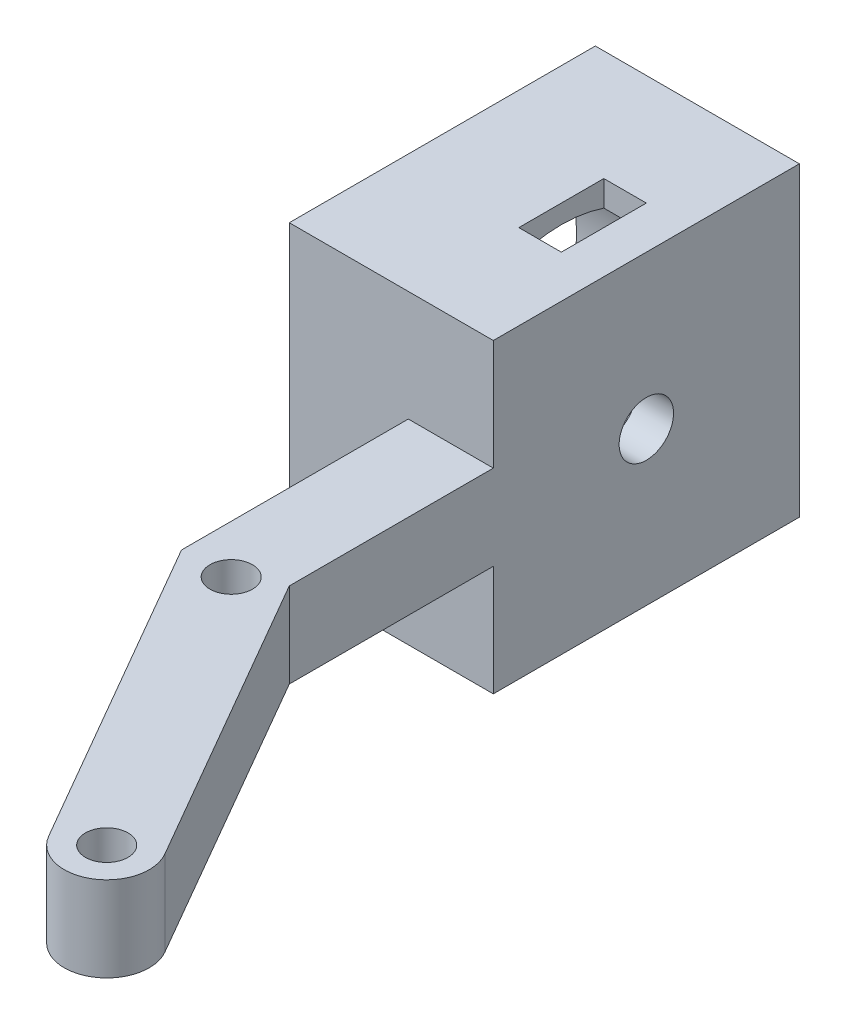
SolidWorks part; units mm, degrees
material "AISI 316 Stainless Steel Sheet (SS)"
ref_plane "Front Plane" through (0, 0, 0) normal (0, 0, 1) x (1, 0, 0)
ref_plane "Top Plane" through (0, 0, 0) normal (0, 1, 0) x (1, 0, 0)
ref_plane "Right Plane" through (0, 0, 0) normal (1, 0, 0) x (0, 0, -1)
sketch "Sketch1" plane through (0, 0, 0) normal (0, 1, 0) x (1, 0, 0)
  line L0 (-6.35, -14.4015) -> (-6.35, 2.54)
  line L1 (0, -12.7) -> (0, 25.4)
  line L2 (0, 25.4) -> (-15.24, 25.4)
  line L3 (-15.24, 25.4) -> (-15.24, 2.54)
  line L4 (-15.24, 2.54) -> (-6.35, 2.54)
  line L5 (0, -12.7) -> (12.7, -34.697)
  line L6 (-6.35, -14.4015) -> (7.2007, -37.872)
  line L7 (0, -12.7) -> (-5.4993, -15.875) construction
  arc A0 (7.2007, -37.872) -> (12.7, -34.697) centre (9.9504, -36.2845) ccw
  circle A1 centre (9.9504, -36.2845) radius 1.5875
  circle A2 centre (-2.7496, -14.2875) radius 1.5875
  dimension "D1" = 3.175
  dimension "D2" = 3.175
  dimension "D6" = 3.175
  dimension "D3" = 150
  dimension "D4" = 6.35
  dimension "D8" = 25.4
  dimension "D10" = 15.24
  dimension "D11" = 38.1
  dimension "D12" = 22.86
  dimension "D13" = 12.7
extrude "Boss-Extrude1" add sketch "Sketch1" along normal blind 22.86
sketch "Sketch2" plane through (0, 22.86, 0) normal (0, 1, 0) x (1, 0, 0)
  line L1 (-6.35, -14.4015) -> (8.7882, -40.6217)
  line L2 (0, -12.7) -> (14.2875, -37.4467)
  line L3 (14.2875, -37.4467) -> (8.7882, -40.6217)
  line L4 (-6.35, -14.4015) -> (7.2007, -37.872) construction
  line L5 (12.7, -34.697) -> (0, -12.7) construction
  line L6 (-6.35, 2.54) -> (0, 2.54)
  line L7 (0, -12.7) -> (0, 25.4) construction
  line L8 (0, 2.54) -> (0, -12.7)
  line L9 (-6.35, -14.4015) -> (-6.35, 2.54)
  arc A0 (7.2007, -37.872) -> (12.7, -34.697) centre (9.9504, -36.2845) ccw construction
extrude "Top Cut" cut sketch "Sketch2" against normal blind 8.255
sketch "Sketch4" plane through (0, 0, 0) normal (0, -1, 0) x (1, 0, 0)
  line L0 (-6.35, -2.54) -> (-6.35, 14.4015)
  line L1 (-6.35, 14.4015) -> (7.2007, 37.872) construction
  line L2 (-6.35, -2.54) -> (-6.35, 14.4015) construction
  line L3 (-6.35, 14.4015) -> (8.7882, 40.6217)
  line L4 (8.7882, 40.6217) -> (14.2875, 37.4467)
  line L5 (-6.35, -2.54) -> (0, -2.54)
  line L7 (0, -2.54) -> (0, 12.7)
  line L8 (0, 12.7) -> (14.2875, 37.4467)
  line L9 (12.7, 34.697) -> (0, 12.7) construction
  arc A0 (12.7, 34.697) -> (7.2007, 37.872) centre (9.9504, 36.2845) ccw construction
extrude "Bottom Cut" cut sketch "Sketch4" against normal blind 8.255
sketch "Sketch3" plane through (0, 22.86, 0) normal (0, 1, 0) x (1, 0, 0)
  line L0 (-15.24, 25.4) -> (-16.51, 24.13)
  line L1 (-16.51, 24.13) -> (-15.24, 22.86)
  line L2 (-15.24, 25.4) -> (-15.24, 2.54) construction
  line L12 (-15.24, 25.4) -> (0, 25.4)
  line L13 (0, 25.4) -> (0, 0)
  line L14 (0, 2.54) -> (0, 25.4) construction
  line L16 (-16.51, 21.59) -> (-15.24, 20.32)
  line L17 (-15.24, 22.86) -> (-16.51, 21.59)
  line L18 (-16.51, 19.05) -> (-15.24, 17.78)
  line L19 (-15.24, 20.32) -> (-16.51, 19.05)
  line L20 (-16.51, 16.51) -> (-15.24, 15.24)
  line L21 (-15.24, 17.78) -> (-16.51, 16.51)
  line L22 (-16.51, 13.97) -> (-15.24, 12.7)
  line L23 (-15.24, 15.24) -> (-16.51, 13.97)
  line L24 (-16.51, 11.43) -> (-15.24, 10.16)
  line L25 (-15.24, 12.7) -> (-16.51, 11.43)
  line L26 (-16.51, 8.89) -> (-15.24, 7.62)
  line L27 (-15.24, 10.16) -> (-16.51, 8.89)
  line L28 (-16.51, 6.35) -> (-15.24, 5.08)
  line L29 (-15.24, 7.62) -> (-16.51, 6.35)
  line L30 (-16.51, 3.81) -> (-15.24, 2.54)
  line L31 (-15.24, 5.08) -> (-16.51, 3.81)
  line L32 (-16.51, 1.27) -> (-15.24, 0)
  line L33 (-15.24, 2.54) -> (-16.51, 1.27)
  line L34 (-15.24, 0) -> (0, 0)
  dimension "D1" = 2.54
  dimension "D2" = 135
  dimension "D3" = 10
extrude "Boss-Extrude2" [suppressed] add sketch "Sketch3" against normal up to surface (5.08 mm away) contours L13 L34 L32 L33 L30 L31 L28 L29 L26 L27 L24 L25 L22 L23 L20 L21 L18 L19 L16 L17 L1 L0 L12 up to face at (-7.62, 0, -13.97)
sketch "Sketch5" plane through (-15.24, 0, 0) normal (-1, 0, 0) x (0, 0, 1)
  line L1 (-25.4, 0) -> (-2.54, 0)
  line L2 (-25.4, 0) -> (-25.4, 22.86)
  line L3 (-25.4, 22.86) -> (-2.54, 22.86)
  line L4 (-2.54, 0) -> (-2.54, 22.86)
  line L5 (-25.4, 0) -> (-2.54, 22.86) construction
  line L6 (-25.4, 22.86) -> (-2.54, 0) construction
  circle A0 centre (-13.97, 11.43) radius 10.033
  point P0 (-13.97, 11.43)
  dimension "D1" = 20.066
extrude "Cut-Extrude1" cut sketch "Sketch5" against normal blind 12.446 contours A0 region at (-15.24, 11.43, -13.97)
sketch "Sketch7" plane through (0, 0, 0) normal (1, 0, 0) x (0, 0, -1)
  line L0 (2.54, 22.86) -> (25.4, 22.86) construction
  line L1 (2.54, 0) -> (25.4, 0)
  line L2 (2.54, 0) -> (2.54, 22.86)
  line L3 (2.54, 22.86) -> (25.4, 22.86)
  line L4 (25.4, 0) -> (25.4, 22.86)
  line L5 (2.54, 0) -> (25.4, 22.86) construction
  line L6 (2.54, 22.86) -> (25.4, 0) construction
  line L7 (25.4, 22.86) -> (25.4, 0) construction
  line L9 (2.54, 0) -> (25.4, 0) construction
  circle A0 centre (13.97, 11.43) radius 2.032
  point P0 (13.97, 11.43)
  point P12 (0, 0)
  dimension "D1" = 4.064
extrude "Cut-Extrude2" cut sketch "Sketch7" against normal through all contours A0 region at (0, 11.43, -13.97)
sketch "Sketch8" plane through (0, 22.86, 0) normal (0, 1, 0) x (1, 0, 0)
  line L0 (0, 2.54) -> (0, 25.4) construction
  line L1 (-6.35, 10.795) -> (-3.175, 10.795)
  line L2 (-6.35, 10.795) -> (-6.35, 17.145)
  line L3 (-6.35, 17.145) -> (-3.175, 17.145)
  line L4 (-3.175, 10.795) -> (-3.175, 17.145)
  line L5 (-6.35, 10.795) -> (-3.175, 17.145) construction
  line L6 (-6.35, 17.145) -> (-3.175, 10.795) construction
  line L7 (-15.24, 25.4) -> (-15.24, 2.54) construction
  line L11 (-15.24, 24.003) -> (-15.24, 3.937) construction
  point P0 (-4.7625, 13.97)
  point P12 (-15.24, 13.97)
  dimension "D1" = 3.175
  dimension "D2" = 6.35
  dimension "D3" = 3.175
extrude "Cut-Extrude3" cut sketch "Sketch8" against normal up to surface (1.9126 mm away) up to face at (-2.794, 11.43, -3.937)
